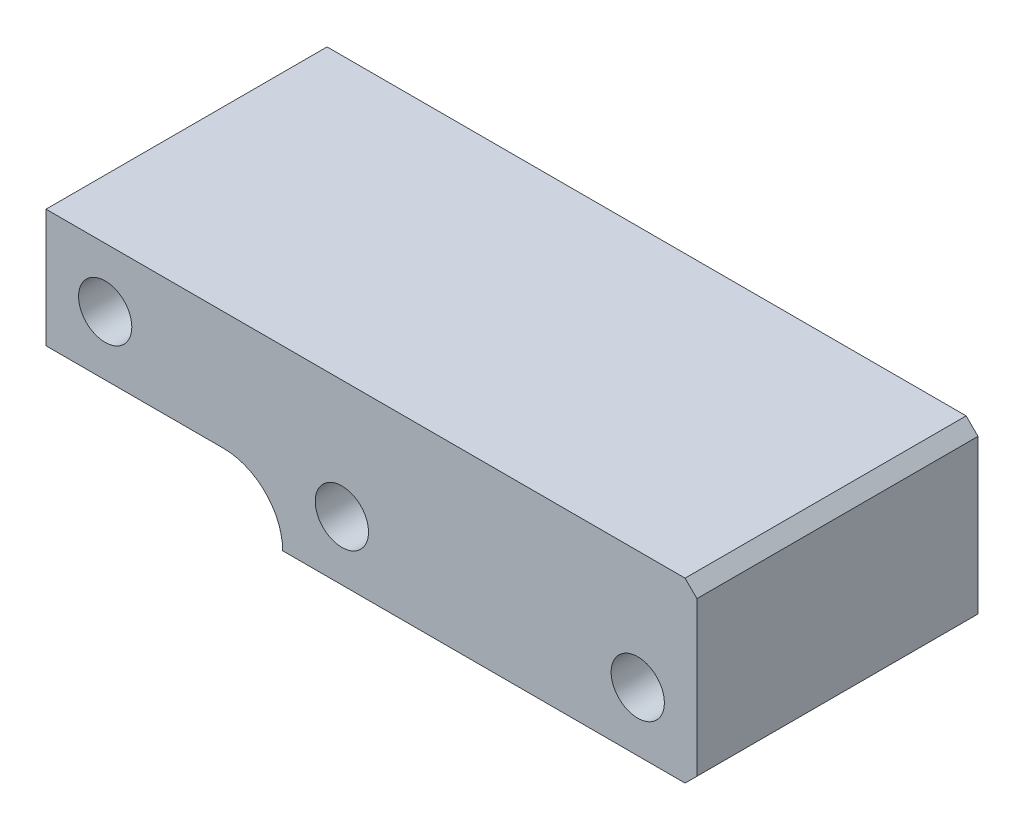
SolidWorks part; units mm, degrees
material "ABS"
ref_plane "前视基准面" through (0, 0, 0) normal (0, 0, 1) x (1, 0, 0)
ref_plane "上视基准面" through (0, 0, 0) normal (0, 1, 0) x (1, 0, 0)
ref_plane "右视基准面" through (0, 0, 0) normal (1, 0, 0) x (0, 0, -1)
sketch "草图1" plane through (0, 0, 0) normal (0, 0, 1) x (1, 0, 0)
  line L0 (35, 0) -> (25, 0) construction
  line L2 (-35, 0) -> (-35, -10)
  line L3 (-35, -10) -> (35, -10)
  line L4 (35, 10) -> (35, -10)
  line L5 (0, 0) -> (35, -10) construction
  line L6 (-35, -10) -> (35, 10) construction
  line L7 (-35, 0) -> (-25, 0) construction
  line L8 (35, 10) -> (35, 20)
  line L9 (35, 20) -> (-35, 20)
  line L10 (-35, 20) -> (-65, 20)
  line L11 (-65, 20) -> (-75, 20)
  line L12 (-75, 20) -> (-75, 0)
  line L13 (-75, 0) -> (-35, 0)
  line L14 (-75, 10) -> (-65, 10) construction
  circle A0 centre (-25, 0) radius 4.5
  circle A1 centre (25, 0) radius 4.5
  circle A2 centre (-65, 10) radius 4.5
  point P0 (0, 0)
  dimension "D1" = 70
  dimension "D5" = 9
  dimension "D6" = 9
  dimension "D7" = 40
  dimension "D9" = 9
  dimension "D3" = 10
  dimension "D4" = 10
  dimension "D8" = 10
extrude "凸台-拉伸1" add sketch "草图1" along normal blind 47.5
fillet "圆角1" radius 10 1 edges at (-35, 0, 23.75)
chamfer "倒角1" distance 2 angle 45 2 edges at (35, -10, 23.75) (35, 20, 23.75)
